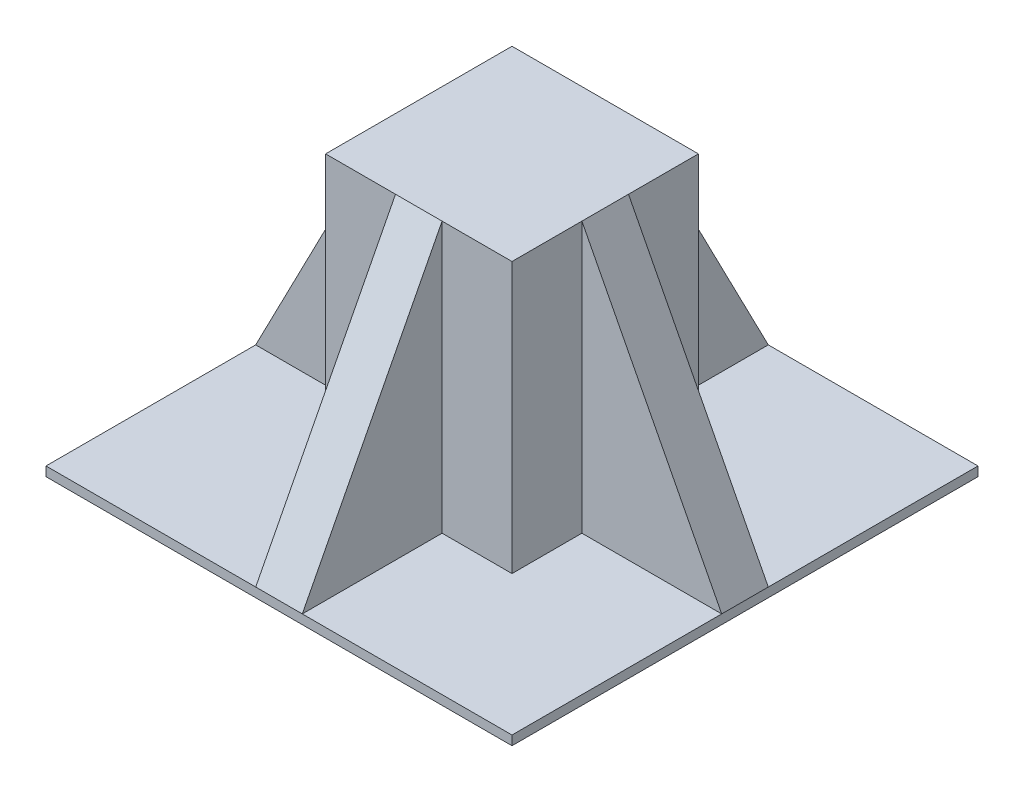
SolidWorks part; units mm, degrees
ref_plane "Alzado" through (0, 0, 0) normal (0, 0, 1) x (1, 0, 0)
ref_plane "Planta" through (0, 0, 0) normal (0, 1, 0) x (1, 0, 0)
ref_plane "Vista lateral" through (0, 0, 0) normal (1, 0, 0) x (0, 0, -1)
sketch "Croquis2" plane through (0, 0, 0) normal (0, 1, 0) x (1, 0, 0)
  line L1 (-50, -50) -> (50, -50)
  line L2 (-50, -50) -> (-50, 50)
  line L3 (-50, 50) -> (50, 50)
  line L4 (50, -50) -> (50, 50)
  line L5 (-50, -50) -> (50, 50) construction
  line L6 (-50, 50) -> (50, -50) construction
  line L7 (-20, -20) -> (20, -20)
  line L8 (-20, -20) -> (-20, 20)
  line L9 (-20, 20) -> (20, 20)
  line L10 (20, -20) -> (20, 20)
  line L11 (-20, -20) -> (20, 20) construction
  line L12 (-20, 20) -> (20, -20) construction
  point P0 (0, 0)
  point P6 (0, 0)
  dimension "D1" = 100
  dimension "D2" = 100
  dimension "D3" = 40
extrude "Saliente-Extruir1" add sketch "Croquis2" along normal blind 2
extrude "Saliente-Extruir2" add sketch "Croquis2<2>" along normal blind 60 contours L7 L10 L9 L8 region at (0, 0, 0)
sketch "Croquis2<2>" plane through (0, 0, 0) normal (0, 1, 0) x (1, 0, 0) same geometry as "Croquis2"
sketch "Croquis4" plane through (0, 0, 0) normal (1, 0, 0) x (0, 0, -1)
  line L0 (20, 60) -> (50, 2)
  line L1 (50, 2) -> (20, 2)
  line L2 (20, 2) -> (20, 60)
  line L3 (-20, 2) -> (-50, 2)
  line L4 (-50, 2) -> (-20, 60)
  line L5 (-20, 60) -> (-20, 2)
extrude "Saliente-Extruir3" add sketch "Croquis4" along normal blind 5 and the other way blind 5
sketch "Croquis5" plane through (0, 0, 0) normal (0, 0, 1) x (1, 0, 0)
  line L0 (20, 60) -> (50, 2)
  line L1 (50, 2) -> (20, 2)
  line L2 (20, 2) -> (20, 60)
  line L3 (-20, 60) -> (-50, 2)
  line L4 (-50, 2) -> (-20, 2)
  line L5 (-20, 2) -> (-20, 60)
extrude "Saliente-Extruir4" add sketch "Croquis5" along normal blind 5 and the other way blind 5
